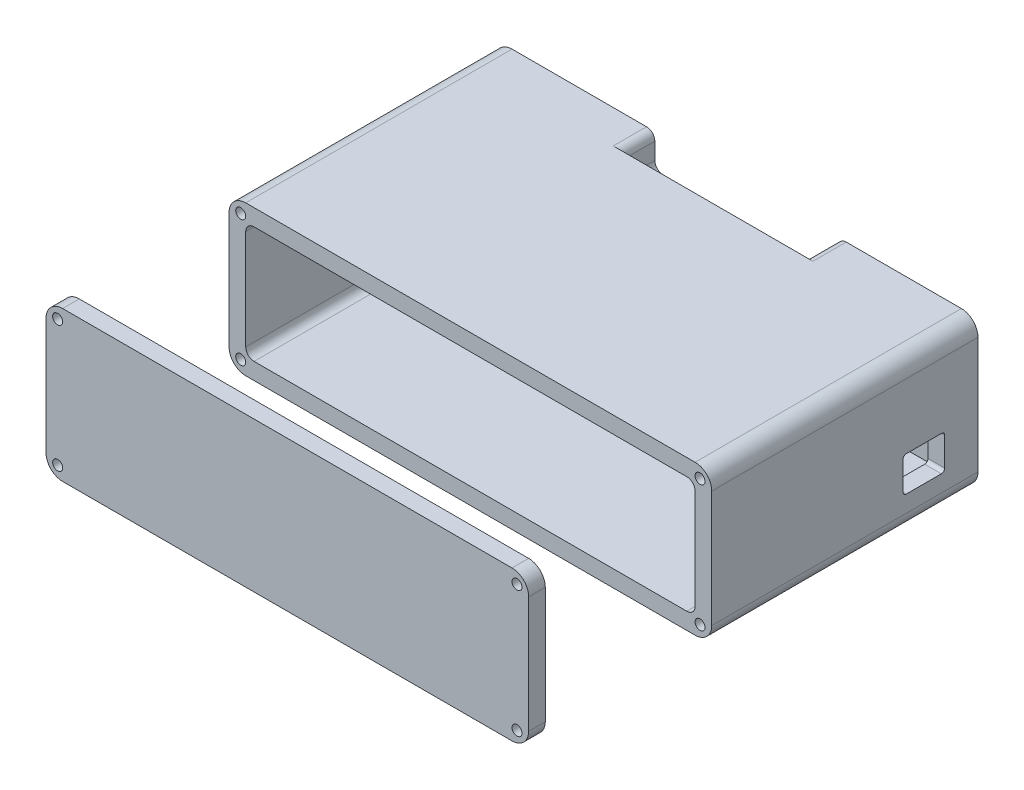
SolidWorks part; units mm, degrees
ref_plane "Front Plane" through (0, 0, 0) normal (0, 0, 1) x (1, 0, 0)
ref_plane "Top Plane" through (0, 0, 0) normal (0, 1, 0) x (1, 0, 0)
ref_plane "Right Plane" through (0, 0, 0) normal (1, 0, 0) x (0, 0, -1)
sketch "Sketch1" plane through (0, 0, 0) normal (0, 0, 1) x (1, 0, 0)
  line L1 (0, 0) -> (145, 0)
  line L2 (0, 0) -> (0, -45)
  line L3 (0, -45) -> (145, -45)
  line L4 (145, 0) -> (145, -45)
  dimension "D1" = 145
  dimension "D2" = 45
extrude "Boss-Extrude1" add sketch "Sketch1" along normal blind 80
sketch "Sketch2" plane through (0, 0, 80) normal (0, 0, 1) x (1, 0, 0)
  line L0 (0, 0) -> (0, -45) construction
  line L1 (5, -5) -> (140, -5)
  line L2 (5, -5) -> (5, -40)
  line L3 (5, -40) -> (140, -40)
  line L4 (140, -5) -> (140, -40)
  line L5 (0, -45) -> (145, -45) construction
  line L6 (145, -45) -> (145, 0) construction
  line L7 (145, 0) -> (0, 0) construction
  dimension "D1" = 5
  dimension "D2" = 5
  dimension "D3" = 5
  dimension "D4" = 5
extrude "Cut-Extrude1" cut sketch "Sketch2" against normal blind 75
sketch "Sketch4" plane through (0, 0, 5) normal (0, 0, 1) x (1, 0, 0)
  line L0 (5, -5) -> (5, -40) construction
  line L1 (5, -40) -> (140, -40) construction
  circle A0 centre (22.5, -24.5) radius 14
  point P4 (0, 0)
  point P7 (0, 0)
  dimension "D1" = 17.5
  dimension "D2" = 15.5
extrude "Cut-Extrude4" cut sketch "Sketch4" against normal blind 20
sketch "Sketch8" plane through (0, 0, 0) normal (0, 0, -1) x (-1, 0, 0)
  line L0 (-145, 0) -> (0, 0) construction
  line L1 (-102.9084, 0) -> (-47.9084, 0)
  line L2 (-102.9084, 0) -> (-102.9084, -10)
  line L3 (-102.9084, -10) -> (-47.9084, -10)
  line L4 (-47.9084, 0) -> (-47.9084, -10)
  dimension "D1" = 55
  dimension "D2" = 10
extrude "Cut-Extrude7" cut sketch "Sketch8" against normal blind 10
fillet "Fillet4" radius 5 4 edges at (145, -45, 40) (145, 0, 40) (0, -45, 40) (0, 0, 40)
fillet "Fillet5" radius 2.5 4 edges at (140, -40, 42.5) (140, -5, 42.5) (5, -40, 42.5) (5, -5, 42.5)
ref_plane "Plane10" through (72.5, 0, 0) normal (-1, 0, 0) x (0, 0, 1)
ref_plane "Plane11" through (0, -22.5, 0) normal (0, 1, 0) x (1, 0, 0)
sketch "Sketch9" plane through (0, 0, 80) normal (0, 0, 1) x (1, 0, 0)
  line L4 (72.5, 37.3266) -> (72.5, -37.3266) construction
  line L5 (44, -22.5) -> (-44, -22.5) construction
  line L6 (0, -5) -> (0, -40) construction
  line L7 (140, 0) -> (5, 0) construction
  circle A0 centre (3.5, -3.5) radius 1.5
  circle A1 centre (141.5, -3.5) radius 1.5
  circle A2 centre (141.5, -41.5) radius 1.5
  circle A3 centre (3.5, -41.5) radius 1.5
  point P4 (0, 0)
  dimension "D1" = 3.5
  dimension "D2" = 3.5
extrude "Cut-Extrude8" cut sketch "Sketch9" against normal blind 10
sketch "Sketch10" plane through (140, 0, 0) normal (-1, 0, 0) x (0, 0, 1)
  line L0 (5, -37.5) -> (5, -7.5) construction
  line L1 (10, -24.5) -> (22.5, -24.5)
  line L2 (10, -24.5) -> (10, -35)
  line L3 (10, -35) -> (22.5, -35)
  line L4 (22.5, -24.5) -> (22.5, -35)
  line L5 (80, -40) -> (5, -40) construction
  dimension "D1" = 12.5
  dimension "D2" = 10.5
  dimension "D3" = 5
  dimension "D4" = 5
extrude "Cut-Extrude9" cut sketch "Sketch10" against normal blind 5
fillet "Fillet11" radius 1 4 edges at (142.5, -35, 10) (142.5, -35, 22.5) (142.5, -24.5, 22.5) (142.5, -24.5, 10)
fillet "Fillet13" radius 2.5 4 edges at (102.9084, 0, 5) (47.9084, 0, 5) (47.9084, -10, 2.5) (102.9084, -10, 2.5)
sketch "Sketch11" plane through (0, 0, 5) normal (0, 0, 1) x (1, 0, 0)
  line L0 (5, -7.5) -> (5, -37.5) construction
  line L1 (7.5, -40) -> (137.5, -40) construction
  circle A0 centre (8, -11.2562) radius 1.5
  circle A1 centre (8, -37) radius 1.5
  dimension "D1" = 3
  dimension "D2" = 3
  dimension "D3" = 3
extrude "Cut-Extrude10" cut sketch "Sketch11" against normal blind 5
ref_plane "Plane12" through (0, 0, 130) normal (0, 0, 1) x (1, 0, 0)
sketch "Sketch12" plane through (0, 0, 130) normal (0, 0, 1) x (1, 0, 0)
  line L1 (0, 0) -> (145, 0)
  line L2 (0, 0) -> (0, -45)
  line L3 (0, -45) -> (145, -45)
  line L4 (145, 0) -> (145, -45)
  dimension "D1" = 145
  dimension "D2" = 45
extrude "Boss-Extrude2" add sketch "Sketch12" along normal blind 5 separate body
fillet "Fillet14" radius 5 4 edges at (145, -45, 132.5) (145, 0, 132.5) (0, -45, 132.5) (0, 0, 132.5)
sketch "Sketch13" plane through (0, 0, 135) normal (0, 0, 1) x (1, 0, 0)
  line L0 (140, 0) -> (5, 0) construction
  line L1 (0, -5) -> (0, -40) construction
  line L2 (72.5, 37.3266) -> (72.5, -37.3266) construction
  line L3 (44, -22.5) -> (-44, -22.5) construction
  circle A0 centre (3.5, -3.5) radius 1.5
  circle A1 centre (141.5, -3.5) radius 1.5
  circle A2 centre (141.5, -41.5) radius 1.5
  circle A3 centre (3.5, -41.5) radius 1.5
  dimension "D1" = 3.5
  dimension "D2" = 3.5
extrude "Cut-Extrude11" cut sketch "Sketch13" against normal blind 5
